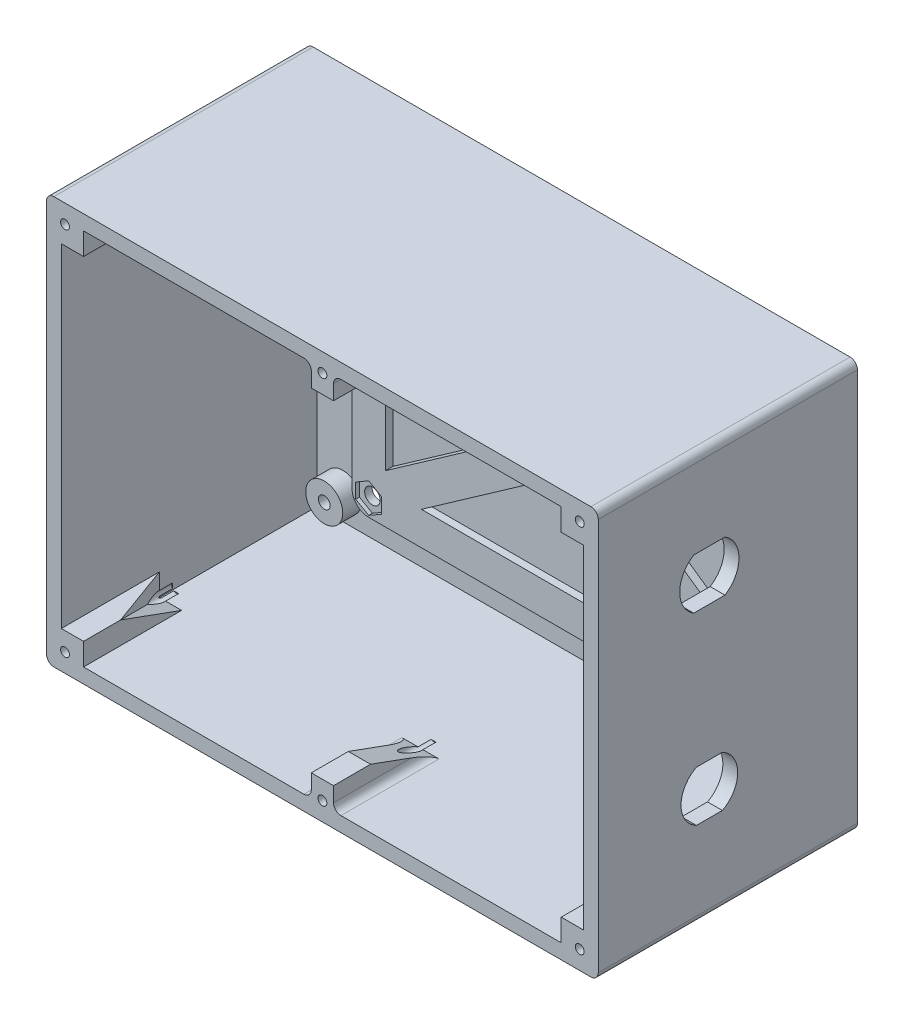
SolidWorks part; units mm, degrees
ref_plane "Přední rovina" through (0, 0, 0) normal (0, 0, 1) x (1, 0, 0)
ref_plane "Horní rovina" through (0, 0, 0) normal (0, 1, 0) x (1, 0, 0)
ref_plane "Pravá rovina" through (0, 0, 0) normal (1, 0, 0) x (0, 0, -1)
sketch "Skica1" plane through (0, 0, 0) normal (0, 0, 1) x (1, 0, 0)
  line L1 (-50, -50) -> (50, -50) construction
  line L2 (-50, -50) -> (-50, 50) construction
  line L3 (-50, 50) -> (50, 50) construction
  line L4 (50, -50) -> (50, 50) construction
  line L5 (-50, -50) -> (50, 50) construction
  line L6 (-50, 50) -> (50, -50) construction
  line L7 (-51, -51) -> (90, -51)
  line L8 (-51, -51) -> (-51, 51)
  line L9 (-51, 51) -> (90, 51)
  line L10 (90, -51) -> (90, 51)
  line L11 (-55, -55) -> (94, -55)
  line L12 (-55, -55) -> (-55, 55)
  line L13 (-55, 55) -> (94, 55)
  line L14 (94, -55) -> (94, 55)
  point P0 (0, 0)
  dimension "D1" = 100
  dimension "D2" = 2
  dimension "D3" = 2
  dimension "D4" = 2
  dimension "D5" = 40
  dimension "D6" = 4
  dimension "D7" = 4
  dimension "D8" = 4
  dimension "D9" = 4
extrude "Přidat vysunutím1" add sketch "Skica1" along normal blind 70
extrude "Přidat vysunutím2" add sketch "Skica1<3>" along normal blind 1 contours L7 L10 L9 L8 region at (19.5, 0, 0)
sketch "Skica1<3>" plane through (0, 0, 0) normal (0, 0, 1) x (1, 0, 0) same geometry as "Skica1"
sketch "Skica2" plane through (0, 0, 1) normal (0, 0, 1) x (1, 0, 0)
  line L0 (90, 51) -> (-51, 51) construction
  line L1 (-49, -49) -> (49, -49) construction
  line L2 (-49, -49) -> (-49, 49) construction
  line L3 (-49, 49) -> (49, 49) construction
  line L20 (49, -49) -> (49, 49) construction
  line L21 (-49, -49) -> (49, 49) construction
  line L22 (-49, 49) -> (49, -49) construction
  line L24 (-44, -44) -> (44, -44) construction
  line L25 (-44, -44) -> (-44, 44) construction
  line L26 (-44, 44) -> (44, 44) construction
  line L27 (44, -44) -> (44, 44) construction
  line L28 (-44, -44) -> (44, 44) construction
  line L29 (-44, 44) -> (44, -44) construction
  circle A0 centre (-44, 44) radius 1.6
  circle A1 centre (44, 44) radius 1.6
  circle A2 centre (44, -44) radius 1.6
  circle A3 centre (-44, -44) radius 1.6
  circle A4 centre (-44, 44) radius 5
  circle A5 centre (44, 44) radius 5
  circle A6 centre (44, -44) radius 5
  circle A7 centre (-44, -44) radius 5
  point P0 (0, 0)
  point P7 (0, 0)
  dimension "D3" = 3.2
  dimension "D1" = 2
  dimension "D2" = 5
extrude "Přidat vysunutím3" add sketch "Skica2" along normal blind 5
extrude "Odebrat vysunutím1" cut sketch "Skica2<2>" against normal through all both and the other way through all contours A0 | A1 | A2 | A3 region at (-44, 44, 1) region at (44, 44, 1) region at (44, -44, 1) region at (-44, -44, 1)
sketch "Skica2<2>" plane through (0, 0, 1) normal (0, 0, 1) x (1, 0, 0) same geometry as "Skica2"
sketch "Skica6" plane through (94, 0, 0) normal (1, 0, 0) x (0, 0, -1)
  line L0 (-40, -55) -> (-40, 55) construction
  line L1 (-70, -55) -> (0, -55) construction
  line L2 (-70, 55) -> (0, 55) construction
  line L3 (-44.2143, 31.8) -> (-35.7857, 31.8)
  line L4 (-44.2143, 18.2) -> (-35.7857, 18.2)
  line L6 (0, -55) -> (0, 55) construction
  line L7 (-43.5046, -18.2) -> (-36.4954, -18.2)
  line L8 (-43.5046, -31.8) -> (-36.4954, -31.8)
  arc A0 (-43.5046, -18.2) -> (-43.5046, -31.8) centre (-40, -25) ccw
  arc A1 (-44.2143, 31.8) -> (-44.2143, 18.2) centre (-40, 25) ccw
  arc A2 (-35.7857, 18.2) -> (-35.7857, 31.8) centre (-40, 25) ccw
  arc A3 (-36.4954, -31.8) -> (-36.4954, -18.2) centre (-40, -25) ccw
  dimension "D1" = 15.3
  dimension "D2" = 16
  dimension "D3" = 13.6
  dimension "D4" = 30
  dimension "D5" = 30
  dimension "D6" = 40
  dimension "D7" = 13.6
extrude "Odebrat vysunutím2" cut sketch "Skica6" against normal up to surface (4 mm away) up to face at (90, 0, 35.5)
sketch "Skica7" plane through (0, 0, 1) normal (0, 0, 1) x (1, 0, 0)
  line L0 (94, 55) -> (-55, 55) construction
  line L1 (-35, -40) -> (79, -40) construction
  line L2 (-35, -40) -> (-35, -37.9) construction
  line L3 (-35, 40) -> (-32.9, 40) construction
  line L4 (79, -40) -> (79, 35.5) construction
  line L5 (-55, -55) -> (94, -55) construction
  line L6 (-55, 55) -> (-55, -55) construction
  line L7 (94, -55) -> (94, 55) construction
  line L8 (76.9, 40) -> (79, 40) construction
  line L9 (74.5, -31.3446) -> (29.8339, 0)
  line L10 (64.7536, 35.5) -> (22, 5.4975)
  line L11 (-20.7536, -35.5) -> (22, -5.4975)
  line L12 (-39.5, 40) -> (-39.5, -40)
  line L13 (-30.5, -31.3446) -> (-30.5, 31.3446)
  line L14 (-35, -44.5) -> (39.0251, -44.5)
  line L15 (64.7536, -35.5) -> (-20.7536, -35.5)
  line L16 (83.5, -40) -> (83.5, 40)
  line L17 (22, -5.4975) -> (64.7536, -35.5)
  line L18 (22, 5.4975) -> (-20.7536, 35.5)
  line L19 (39.0251, 44.5) -> (-35, 44.5)
  line L20 (79, 44.5) -> (48.9749, 44.5)
  line L21 (74.5, 31.3446) -> (74.5, -31.3446)
  line L22 (29.8339, 0) -> (74.5, 31.3446)
  line L23 (14.1661, 0) -> (-30.5, -31.3446)
  line L24 (-30.5, 31.3446) -> (14.1661, 0)
  line L25 (48.9749, -44.5) -> (79, -44.5)
  line L26 (-35, -35.5) -> (-35, 35.5) construction
  line L27 (79, 37.9) -> (79, 40) construction
  line L28 (-20.7536, 35.5) -> (64.7536, 35.5)
  line L30 (71.1661, 40) -> (74.5, 40) construction
  line L31 (-35, 37.9) -> (-35, 40) construction
  circle A0 centre (-35, 40) radius 2.1
  arc A1 (-35, 44.5) -> (-39.5, 40) centre (-35, 40) ccw
  circle A2 centre (79, 40) radius 2.1
  arc A3 (83.5, 40) -> (79, 44.5) centre (79, 40) ccw
  circle A4 centre (79, -40) radius 2.1
  arc A5 (79, -44.5) -> (83.5, -40) centre (79, -40) ccw
  circle A6 centre (-35, -40) radius 2.1
  arc A7 (-39.5, -40) -> (-35, -44.5) centre (-35, -40) ccw
  circle A8 centre (44, 44) radius 5 construction
  circle A9 centre (44, -44) radius 5 construction
  arc A10 (39.0251, 44.5) -> (48.9749, 44.5) centre (44, 44) ccw
  arc A11 (48.9749, -44.5) -> (39.0251, -44.5) centre (44, -44) ccw
  point P38 (0, 0)
  point P40 (79, 44.5)
  point P46 (79, 44.5)
  point P47 (74.5, 40)
  point P48 (74.5358, -40.5661)
  point P49 (74.5, -40)
  point P50 (79, -35.5)
  point P51 (-35, -35.5)
  point P52 (0, 0)
  point P53 (0, 0)
  point P54 (-30.5, 41.4416)
  point P55 (-30.5, 40)
  point P56 (-35, -35.5)
  point P57 (-33.8124, -35.5)
  point P58 (-35, -35.5)
  point P59 (-35.132, -35.5019)
  point P60 (79.1257, 44.4982)
  dimension "D5" = 4.2
  dimension "D6" = 9
  dimension "D1" = 15
  dimension "D2" = 15
  dimension "D3" = 20
  dimension "D4" = 15
extrude "Přidat vysunutím4" add sketch "Skica7" along normal blind 2
extrude "Odebrat vysunutím3" cut sketch "Skica7<2>" against normal through all contours A0 | A2 | A4 | A6 region at (-35, 40, 1) region at (79, 40, 1) region at (79, -40, 1) region at (-35, -40, 1)
sketch "Skica7<2>" plane through (0, 0, 1) normal (0, 0, 1) x (1, 0, 0) same geometry as "Skica7"
sketch "Skica8" plane through (0, 0, 3) normal (0, 0, 1) x (1, 0, 0)
  line L1 (-35, 35.9585) -> (-31.5, 37.9793)
  line L2 (-31.5, 37.9793) -> (-31.5, 42.0207)
  line L3 (-31.5, 42.0207) -> (-35, 44.0415)
  line L4 (-35, 44.0415) -> (-38.5, 42.0207)
  line L5 (-38.5, 42.0207) -> (-38.5, 37.9793)
  line L6 (-38.5, 37.9793) -> (-35, 35.9585)
  line L7 (-35, -35.9585) -> (-38.5, -37.9793)
  line L8 (-38.5, -37.9793) -> (-38.5, -42.0207)
  line L9 (-38.5, -42.0207) -> (-35, -44.0415)
  line L10 (-35, -44.0415) -> (-31.5, -42.0207)
  line L11 (-31.5, -42.0207) -> (-31.5, -37.9793)
  line L12 (-31.5, -37.9793) -> (-35, -35.9585)
  line L13 (79, -35.9585) -> (75.5, -37.9793)
  line L14 (75.5, -37.9793) -> (75.5, -42.0207)
  line L15 (75.5, -42.0207) -> (79, -44.0415)
  line L16 (79, -44.0415) -> (82.5, -42.0207)
  line L17 (82.5, -42.0207) -> (82.5, -37.9793)
  line L18 (82.5, -37.9793) -> (79, -35.9585)
  line L19 (79, 35.9585) -> (82.5, 37.9793)
  line L20 (82.5, 37.9793) -> (82.5, 42.0207)
  line L21 (82.5, 42.0207) -> (79, 44.0415)
  line L22 (79, 44.0415) -> (75.5, 42.0207)
  line L23 (75.5, 42.0207) -> (75.5, 37.9793)
  line L24 (75.5, 37.9793) -> (79, 35.9585)
  circle A4 centre (-35, 40) radius 3.5 construction
  circle A5 centre (-35, -40) radius 3.5 construction
  circle A6 centre (79, -40) radius 3.5 construction
  circle A7 centre (79, 40) radius 3.5 construction
  dimension "D1" = 7
extrude "Odebrat vysunutím4" cut sketch "Skica8" against normal blind 1
sketch "Skica9" plane through (0, 0, 0) normal (0, 0, -1) x (-1, 0, 0)
  line L1 (-44, 40.8246) -> (-41.25, 42.4123)
  line L2 (-41.25, 42.4123) -> (-41.25, 45.5877)
  line L3 (-41.25, 45.5877) -> (-44, 47.1754)
  line L4 (-44, 47.1754) -> (-46.75, 45.5877)
  line L5 (-46.75, 45.5877) -> (-46.75, 42.4123)
  line L6 (-46.75, 42.4123) -> (-44, 40.8246)
  line L19 (-44, -47.1754) -> (-41.25, -45.5877)
  line L20 (-41.25, -45.5877) -> (-41.25, -42.4123)
  line L21 (-41.25, -42.4123) -> (-44, -40.8246)
  line L22 (-44, -40.8246) -> (-46.75, -42.4123)
  line L23 (-46.75, -42.4123) -> (-46.75, -45.5877)
  line L24 (-46.75, -45.5877) -> (-44, -47.1754)
  line L25 (44, -47.1754) -> (46.75, -45.5877)
  line L26 (46.75, -45.5877) -> (46.75, -42.4123)
  line L27 (46.75, -42.4123) -> (44, -40.8246)
  line L28 (44, -40.8246) -> (41.25, -42.4123)
  line L29 (41.25, -42.4123) -> (41.25, -45.5877)
  line L30 (41.25, -45.5877) -> (44, -47.1754)
  line L31 (44, 40.8246) -> (46.75, 42.4123)
  line L32 (46.75, 42.4123) -> (46.75, 45.5877)
  line L33 (46.75, 45.5877) -> (44, 47.1754)
  line L34 (44, 47.1754) -> (41.25, 45.5877)
  line L35 (41.25, 45.5877) -> (41.25, 42.4123)
  line L36 (41.25, 42.4123) -> (44, 40.8246)
  circle A0 centre (-44, 44) radius 2.75 construction
  circle A3 centre (-44, -44) radius 2.75 construction
  circle A4 centre (44, -44) radius 2.75 construction
  circle A5 centre (44, 44) radius 2.75 construction
  dimension "D1" = 5.5
extrude "Odebrat vysunutím5" cut sketch "Skica9" against normal blind 2.5
sketch "Skica10" plane through (0, 0, 70) normal (0, 0, 1) x (1, 0, 0)
  line L0 (90, 51) -> (-51, 51) construction
  line L1 (-51, 51) -> (-45, 51)
  line L2 (-51, 51) -> (-51, 45)
  line L3 (-51, 45) -> (-45, 45)
  line L4 (-45, 51) -> (-45, 45)
  line L5 (90, 51) -> (84, 51)
  line L6 (90, 51) -> (90, 45)
  line L7 (90, 45) -> (84, 45)
  line L8 (84, 51) -> (84, 45)
  line L9 (90, -51) -> (84, -51)
  line L10 (90, -51) -> (90, -45)
  line L11 (90, -45) -> (84, -45)
  line L12 (84, -51) -> (84, -45)
  line L13 (-51, -51) -> (-45, -51)
  line L14 (-51, -51) -> (-51, -45)
  line L15 (-51, -45) -> (-45, -45)
  line L16 (-45, -51) -> (-45, -45)
  line L17 (16.5, 51) -> (22.5, 51)
  line L18 (16.5, 51) -> (16.5, 45)
  line L19 (16.5, 45) -> (22.5, 45)
  line L20 (22.5, 51) -> (22.5, 45)
  line L21 (-51, -51) -> (90, -51) construction
  line L22 (22.5, -51) -> (16.5, -51)
  line L23 (22.5, -51) -> (22.5, -45)
  line L24 (22.5, -45) -> (16.5, -45)
  line L25 (16.5, -51) -> (16.5, -45)
  line L27 (-55, 55) -> (-55, -55) construction
  point P32 (19.5, -51)
  point P34 (19.5, 45)
  point P38 (-50, 50)
  dimension "D1" = 74.5
  dimension "D2" = 74.5
  dimension "D3" = 6
extrude "Přidat vysunutím5" add sketch "Skica10" against normal blind 10
chamfer "Zkosení1" distance 6 angle 70 10 edges at (-51, 48, 60) (-48, 51, 60) (-48, -51, 60) (-51, -48, 60) (19.5, 51, 60) (19.5, -51, 60) (90, -48, 60) (87, -51, 60) (87, 51, 60) (90, 48, 60) first distance on face at (-48, 48, 60) first distance on face at (-48, -48, 60) first distance on face at (19.5, 48, 60) first distance on face at (19.5, -48, 60) first distance on face at (87, -48, 60) first distance on face at (87, 48, 60)
sketch "Skica11" plane through (0, 0, 70) normal (0, 0, 1) x (1, 0, 0)
  line L1 (-50, -50) -> (89, -50) construction
  line L2 (-50, -50) -> (-50, 50) construction
  line L3 (-50, 50) -> (89, 50) construction
  line L4 (89, -50) -> (89, 50) construction
  line L6 (84, 45) -> (94, 55) construction
  line L7 (-45, -45) -> (-55, -55) construction
  circle A0 centre (-50, 50) radius 1.2
  circle A1 centre (19.5, 50) radius 1.2
  circle A2 centre (89, 50) radius 1.2
  circle A3 centre (89, -50) radius 1.2
  circle A4 centre (19.5, -50) radius 1.2
  circle A5 centre (-50, -50) radius 1.2
  dimension "D1" = 2.4
extrude "Odebrat vysunutím6" cut sketch "Skica11" against normal blind 30
fillet "Zaoblit1" radius 2 4 edges at (94, -55, 35) (-55, -55, 35) (94, 55, 35) (-55, 55, 35)
fillet "Zaoblit2" radius 2 4 edges at (16.5, -51, 56.7576) (22.5, -51, 56.7576) (22.5, 51, 56.7576) (16.5, 51, 56.7576)
